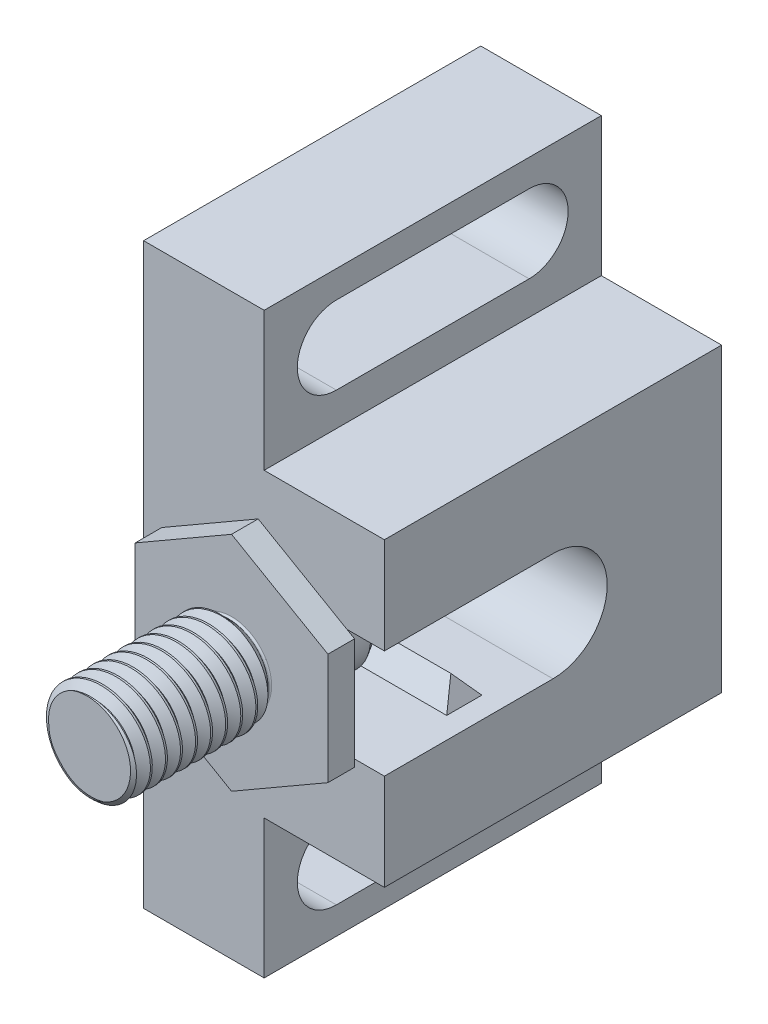
SolidWorks part; units mm, degrees
material "6061-T6 (SS)"
ref_plane "Front Plane" through (0, 0, 0) normal (0, 0, 1) x (1, 0, 0)
ref_plane "Top Plane" through (0, 0, 0) normal (0, 1, 0) x (1, 0, 0)
ref_plane "Right Plane" through (0, 0, 0) normal (1, 0, 0) x (0, 0, -1)
sketch "Sketch1" plane through (0, 0, 0) normal (1, 0, 0) x (0, 0, -1)
  line L0 (13.9954, 0) -> (-13.9954, 0) construction
  line L1 (0, 24.003) -> (0, -24.003) construction
  line L2 (-8.001, 18.5039) -> (8.001, 18.5039) construction
  line L3 (8.001, 21.7424) -> (8.001, 15.2654) construction
  point P0 (0, 18.5039)
  point P4 (0, 0)
  point P8 (0, 0)
  point P17 (8.001, 18.5039)
  dimension "Latch Width" = 27.9908
  dimension "Latch Height" = 48.006
  dimension "Slot Spacing" = 37.0078
  dimension "Slot Width" = 16.002
  dimension "Slot Dia" = 6.477
sketch "Sketch2" plane through (0, 0, 0) normal (0, 0, 1) x (1, 0, 0)
  line L0 (-9.9949, 0) -> (9.9949, 0) construction
  line L1 (-0.4953, 4.5) -> (-0.4953, -4.5) construction
  line L2 (9.9949, 12.4968) -> (9.9949, -12.4968) construction
  point P0 (0.0127, 0)
  point P3 (0, 0)
  point P7 (-9.9949, 0)
  point P10 (-0.4953, 0)
  point P12 (-0.4953, 0)
  dimension "D1" = 10.4902
  dimension "Center Width" = 24.9936
  dimension "Overall Latch Height" = 19.9898
  dimension "Flange Thickness" = 10.0076
  dimension "Catch Width" = 9
sketch "Sketch3" plane through (0, 0, 0) normal (0, 1, 0) x (1, 0, 0)
  line L0 (-4, -28.6773) -> (4, -28.6773) construction
  line L1 (0, 13.9954) -> (0, -13.9954) construction
  line L2 (0, 13.9954) -> (0, -13.9954) construction
  line L3 (4, -28.6773) -> (4, -29.9273) construction
  line L4 (8, -16.6885) -> (-8, -16.6885) construction
  line L5 (8, -16.6885) -> (8, -14.4787) construction
  line L6 (3.5, 0.3803) -> (-3.5, 0.3803) construction
  point P3 (0, -28.6773)
  point P9 (0, -16.6885)
  point P13 (0, 0.3803)
  dimension "D1" = 0.4833
sketch "Sketch4" plane through (0, 0, 0) normal (0, 0, 1) x (1, 0, 0)
  line L0 (9.9949, -12.4968) -> (9.9949, 12.4968)
  line L1 (9.9949, 12.4968) -> (0.0127, 12.4968)
  line L2 (0.0127, 12.4968) -> (0.0127, 24.003)
  line L3 (0.0127, 24.003) -> (-9.9949, 24.003)
  line L4 (-9.9949, 24.003) -> (-9.9949, -24.003)
  line L5 (-9.9949, 0) -> (9.9949, 0) construction
  line L6 (-9.9949, 0) -> (9.9949, 0) construction
  line L7 (0.0127, -24.003) -> (-9.9949, -24.003)
  line L8 (0.0127, -12.4968) -> (0.0127, -24.003)
  line L9 (9.9949, -12.4968) -> (0.0127, -12.4968)
extrude "Boss-Extrude1" add sketch "Sketch4" against normal up to vertex (13.9954 mm away) and the other way up to vertex (13.9954 mm away) up to point (0, 0, -13.9954) other way up to point (0, 0, 13.9954)
sketch "Sketch5" plane through (0.0127, 0, 0) normal (1, 0, 0) x (0, 0, -1)
  line L0 (-8.001, 18.5039) -> (8.001, 18.5039) construction
  line L1 (-8.001, 21.7424) -> (8.001, 21.7424)
  line L2 (-8.001, 15.2654) -> (8.001, 15.2654)
  line L3 (13.9954, 0) -> (-13.9954, 0) construction
  line L4 (13.9954, 0) -> (-13.9954, 0) construction
  line L5 (-8.001, -18.5039) -> (8.001, -18.5039) construction
  line L6 (-8.001, -21.7424) -> (8.001, -21.7424)
  line L7 (-8.001, -15.2654) -> (8.001, -15.2654)
  arc A0 (-8.001, 21.7424) -> (-8.001, 15.2654) centre (-8.001, 18.5039) ccw
  arc A1 (8.001, 15.2654) -> (8.001, 21.7424) centre (8.001, 18.5039) ccw
  arc A2 (-8.001, -21.7424) -> (-8.001, -15.2654) centre (-8.001, -18.5039) cw
  arc A3 (8.001, -15.2654) -> (8.001, -21.7424) centre (8.001, -18.5039) cw
  point P4 (0, 18.5039)
  point P16 (0, -18.5039)
extrude "Cut-Extrude1" cut sketch "Sketch5" against normal through all
sketch "Sketch6" plane through (0, 0, 0) normal (0, 0, 1) x (1, 0, 0)
  line L0 (-0.4953, 0) -> (9.9949, 0) construction
  line L1 (-0.4953, 4.5) -> (-0.4953, -4.5) construction
  line L2 (-0.4953, 4.5) -> (9.9949, 4.5)
  line L3 (9.9949, 12.4968) -> (9.9949, -12.4968) construction
  line L4 (9.9949, 4.5) -> (9.9949, 0)
  line L5 (-9.9949, 0) -> (9.9949, 0) construction
  line L6 (9.9949, 0) -> (-4.9953, 0)
  arc A0 (-0.4953, 4.5) -> (-4.9953, 0) centre (-0.4953, 0) ccw
revolve "Cut-Revolve1" cut sketch "Sketch6" angle 360 about L0
sketch "Sketch7" plane through (0, 0, 13.9954) normal (0, 0, 1) x (1, 0, 0)
  line L0 (-0.4953, 4.5) -> (9.9949, 4.5) construction
  line L1 (9.9949, 4.5) -> (9.9949, 0) construction
  line L2 (-0.4953, 4.5) -> (9.9949, 4.5)
  line L3 (9.9949, 4.5) -> (9.9949, -4.5)
  line L4 (-4.9953, 0) -> (9.9949, 0) construction
  line L5 (-0.4953, -4.5) -> (9.9949, -4.5)
  arc A0 (-0.4953, 4.5) -> (-4.9953, 0) centre (-0.4953, 0) ccw construction
  arc A1 (-0.4953, 4.5) -> (-0.4953, -4.5) centre (-0.4953, 0) ccw
extrude "Cut-Extrude2" cut sketch "Sketch7" against normal up to next
sketch "Sketch8" plane through (9.9949, 0, 0) normal (1, 0, 0) x (0, 0, -1)
  line L0 (-4.1278, -4.5) -> (-7.0458, -4.5)
  line L1 (0, -4.5) -> (-13.9954, -4.5) construction
  line L2 (-7.0458, -4.5) -> (-5.5868, -2.7612)
  line L3 (-5.5868, -2.7612) -> (-4.1278, -4.5)
  line L4 (-13.9954, 4.5) -> (-13.9954, -4.5) construction
  line L5 (0, 0) -> (-13.9954, 0) construction
  line L6 (-5.5868, 2.7612) -> (-4.1278, 4.5)
  line L7 (-7.0458, 4.5) -> (-5.5868, 2.7612)
  line L8 (-4.1278, 4.5) -> (-7.0458, 4.5)
  dimension "D1" = 1.7388
  dimension "D2" = 8.4086
  dimension "D3" = 2.918
extrude "Boss-Extrude2" add sketch "Sketch8" against normal up to surface (14.0434 mm away)
sketch "Sketch9" plane through (0, 0, 13.9954) normal (0, 0, 1) x (1, 0, 0)
  line L0 (9.9949, 4.5) -> (9.9949, 2.7612)
  line L1 (9.9949, 2.7612) -> (7.1053, 2.7612)
  line L2 (-4.0485, 2.7612) -> (9.9949, 2.7612) construction
  line L3 (7.1053, 2.7612) -> (8.2169, 4.5)
  line L4 (-0.4953, 4.5) -> (9.9949, 4.5) construction
  line L5 (8.2169, 4.5) -> (9.9949, 4.5)
  line L6 (0, 0) -> (9.9949, 0) construction
  line L7 (9.9949, -4.5) -> (9.9949, 4.5) construction
  line L8 (8.2169, -4.5) -> (9.9949, -4.5)
  line L9 (7.1053, -2.7612) -> (8.2169, -4.5)
  line L10 (9.9949, -2.7612) -> (7.1053, -2.7612)
  line L11 (9.9949, -4.5) -> (9.9949, -2.7612)
  dimension "D1" = 1.778
  dimension "D2" = 1.1116
extrude "Cut-Extrude3" cut sketch "Sketch9" against normal up to vertex
sketch "Sketch10" plane through (0, 0, 0) normal (0, 1, 0) x (1, 0, 0)
  line L0 (0, -28.6773) -> (0, 0.3803) construction
  line L1 (0, -28.6773) -> (3.6031, -28.6773)
  line L2 (4, -28.2804) -> (4, -17.6689)
  line L3 (4, -17.6689) -> (3.2364, -16.9053)
  line L4 (3.6031, -28.6773) -> (4, -28.2804)
  line L5 (8, -16.6885) -> (-8, -16.6885) construction
  line L6 (3.3262, -16.6885) -> (9.9949, -16.6885)
  line L7 (9.9949, 13.9954) -> (9.9949, -13.9954) construction
  line L8 (9.9949, -16.6885) -> (9.9949, -14.4787)
  line L9 (9.9949, -14.4787) -> (4, -14.4787)
  line L10 (4, -14.4787) -> (4, -9.1453)
  line L11 (4, -9.1453) -> (1.9122, -5.529)
  line L12 (3.5, 0.3803) -> (3.5, -2.7788) construction
  line L13 (0, -28.6773) -> (0, 0.3803)
  arc A0 (1.9122, -5.529) -> (0, 0.3803) centre (0.3243, -2.7788) ccw
  arc A1 (3.2364, -16.9053) -> (3.3262, -16.6885) centre (3.3262, -16.8155) cw
  point P5 (4, -28.6773)
  dimension "D5" = 0.127
  dimension "D1" = 30
  dimension "D2" = 5.3334
  dimension "D3" = 8
  dimension "D4" = 45
  dimension "D6" = 6.6525
revolve "Revolve1" add sketch "Sketch10" angle 360 about L13
sketch "Sketch11" plane through (0, 0, 16.6885) normal (0, 0, 1) x (1, 0, 0)
  line L0 (-9.9949, 0) -> (9.9949, 0) construction
  line L1 (8, 4.6188) -> (0, 9.2376)
  line L2 (0, 9.2376) -> (-8, 4.6188)
  line L3 (-8, 4.6188) -> (-8, -4.6188)
  line L4 (-8, -4.6188) -> (0, -9.2376)
  line L5 (0, -9.2376) -> (8, -4.6188)
  line L6 (8, -4.6188) -> (8, 4.6188)
  circle A0 centre (0, 0) radius 8 construction
extrude "Cut-Extrude4" cut sketch "Sketch11" against normal through all flip side to cut
sketch "Sketch14" plane through (0, 0, 0) normal (1, 0, 0) x (0, 0, -1)
  line L0 (-28.2804, -4) -> (-17.6689, -4) construction
  line L1 (-28.6773, 3.6031) -> (-28.6773, -3.6031) construction
  point P0 (-25.5523, -4)
  dimension "D1" = 3.125
sketch "Sketch12" plane through (0, 0, 28.6773) normal (0, 0, 1) x (1, 0, 0)
  circle A0 centre (0, 0) radius 4 construction
  circle A1 centre (0, 0) radius 4
curve "Helix/Spiral1" pitch 1.25 height 11.9888 turns 9.591
sketch "Sketch13" plane through (0, 0, 0) normal (0, 1, 0) x (1, 0, 0)
  line L0 (4, -29.7711) -> (3.1881, -29.3023)
  line L1 (3.1881, -29.3023) -> (3.1881, -29.1461)
  line L2 (3.1881, -29.1461) -> (4, -28.6773)
  line L3 (4, -28.6773) -> (4, -29.7711)
  line L4 (4, -28.2804) -> (4, -17.6689) construction
  line L5 (-3.6031, -28.6773) -> (3.6031, -28.6773) construction
  line L6 (3.5941, -29.5367) -> (3.5941, -28.9117) construction
  dimension "D1" = 60
  dimension "D2" = 0.1563
  dimension "D3" = 0.625
sweep "Cut-Sweep1" cut profiles "Sketch13" path "Helix/Spiral1"
delete or keep bodies "Body-Delete/Keep 1" [suppressed] type delete bodies bodies 117
delete or keep bodies "Body-Delete/Keep 2" [suppressed] type delete bodies bodies 113
equation "\"D3@Helix/Spiral1\"=\"Thread Length@Sketch3\""
equation "\"D4@Helix/Spiral1\"=\"Thread Pitch@Sketch3\""
equation "\"D2@Sketch13\"=\"Thread Pitch@Sketch3\"*.125"
equation "\"D3@Sketch13\"=\"Thread Pitch@Sketch3\"*.5"
equation "\"D1@Sketch14\"=\"Thread Pitch@Sketch3\"*2.5"
